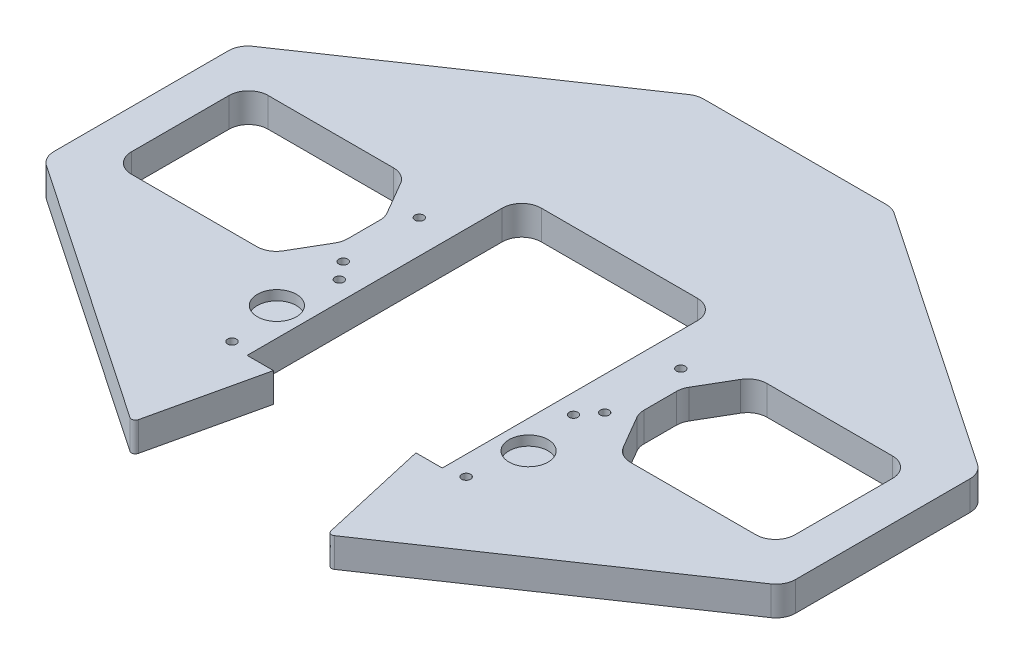
SolidWorks part; units mm, degrees
material "Balsa"
ref_plane "Plan de face" through (0, 0, 0) normal (0, 0, 1) x (1, 0, 0)
ref_plane "Plan de dessus" through (0, 0, 0) normal (0, 1, 0) x (1, 0, 0)
ref_plane "Plan de droite" through (0, 0, 0) normal (1, 0, 0) x (0, 0, -1)
sketch "Esquisse1" plane through (0, 0, 0) normal (0, 1, 0) x (1, 0, 0)
  line L0 (-76.6432, -51.4013) -> (63.3568, 43.5987)
  line L1 (63.3568, 43.5987) -> (163.3568, 43.5987)
  line L2 (-76.6432, -51.4013) -> (-76.6432, -151.4013)
  line L3 (63.3568, -246.4013) -> (163.3568, -246.4013)
  line L4 (303.3568, -51.4013) -> (303.3568, -151.4013)
  line L5 (163.3568, 43.5987) -> (303.3568, -51.4013)
  line L6 (163.3568, -246.4013) -> (303.3568, -151.4013)
  line L7 (-76.6432, -151.4013) -> (63.3568, -246.4013)
  point P0 (-76.6432, 43.5987)
  point P1 (303.3568, -246.4013)
  point P2 (-76.6432, -246.4013)
  point P3 (303.3568, 43.5987)
  dimension "D1" = 380
  dimension "D2" = 290
  dimension "D3" = 140
  dimension "D4" = 95
  dimension "D5" = 140
  dimension "D6" = 95
  dimension "D7" = 140
  dimension "D8" = 95
  dimension "D9" = 95
  dimension "D10" = 140
extrude "Boss.-Extru.1" add sketch "Esquisse1" along normal blind 15 contours L0 L1 L5 L4 L6 L3 L7 L2
sketch "Esquisse6" plane through (0, 0, 246.4013) normal (0, 0, 1) x (1, 0, 0)
  line L1 (63.3568, 15) -> (163.3568, 15)
  line L2 (63.3568, 15) -> (63.3568, 0)
  line L3 (63.3568, 0) -> (163.3568, 0)
  line L4 (163.3568, 15) -> (163.3568, 0)
extrude "Enlèv. mat.-Extru.1" cut sketch "Esquisse6" against normal blind 200
sketch "Esquisse7" plane through (0, 15, 0) normal (0, 1, 0) x (1, 0, 0)
  line L0 (-76.6432, -51.4013) -> (-76.6432, -151.4013) construction
  line L1 (23.3568, -136.4013) -> (-56.6432, -136.4013)
  line L2 (23.3568, -136.4013) -> (23.3568, -66.4013)
  line L3 (23.3568, -66.4013) -> (-56.6432, -66.4013)
  line L4 (-56.6432, -136.4013) -> (-56.6432, -66.4013)
  line L5 (163.3568, -46.4013) -> (63.3568, -46.4013) construction
  line L6 (303.3568, -51.4013) -> (303.3568, -151.4013) construction
  line L7 (283.3568, -136.4013) -> (203.3568, -136.4013)
  line L8 (283.3568, -136.4013) -> (283.3568, -66.4013)
  line L9 (283.3568, -66.4013) -> (203.3568, -66.4013)
  line L10 (203.3568, -136.4013) -> (203.3568, -66.4013)
  dimension "D1" = 70
  dimension "D2" = 20
  dimension "D3" = 80
  dimension "D4" = 20
  dimension "D5" = 70
  dimension "D6" = 80
  dimension "D7" = 20
  dimension "D8" = 20
extrude "Enlèv. mat.-Extru.2" cut sketch "Esquisse7" against normal up to next
sketch "Esquisse8" plane through (0, 15, 0) normal (0, 1, 0) x (1, 0, 0)
  line L0 (203.3568, -66.4013) -> (203.3568, -136.4013) construction
  line L1 (203.3568, -136.4013) -> (283.3568, -136.4013) construction
  line L2 (23.3568, -136.4013) -> (23.3568, -66.4013) construction
  line L3 (-56.6432, -136.4013) -> (23.3568, -136.4013) construction
  circle A0 centre (180.3568, -120.9013) radius 2.25
  circle A1 centre (180.3568, -81.9013) radius 2.25
  circle A2 centre (46.3568, -120.9013) radius 2.25
  circle A3 centre (46.3568, -81.9013) radius 2.25
  dimension "D1" = 4.5
  dimension "D3" = 4.5
  dimension "D11" = 4.5
  dimension "D12" = 4.5
  dimension "D2" = 23
  dimension "D4" = 23
  dimension "D5" = 39
  dimension "D6" = 15.5
  dimension "D7" = 23
  dimension "D8" = 23
  dimension "D9" = 39
  dimension "D10" = 15.5
extrude "Enlèv. mat.-Extru.4" cut sketch "Esquisse8" against normal up to next contours A0 | A2 | A1 | A3
sketch "Esquisse9" plane through (0, 15, 0) normal (0, 1, 0) x (1, 0, 0)
  line L0 (203.3568, -66.4013) -> (203.3568, -136.4013) construction
  line L1 (203.3568, -90.4013) -> (189.3568, -90.4013)
  line L2 (203.3568, -90.4013) -> (203.3568, -112.4013)
  line L3 (203.3568, -112.4013) -> (189.3568, -112.4013)
  line L4 (189.3568, -90.4013) -> (189.3568, -112.4013)
  line L5 (23.3568, -136.4013) -> (23.3568, -66.4013) construction
  line L6 (23.3568, -112.4013) -> (37.3568, -112.4013)
  line L7 (23.3568, -112.4013) -> (23.3568, -90.4013)
  line L8 (23.3568, -90.4013) -> (37.3568, -90.4013)
  line L9 (37.3568, -112.4013) -> (37.3568, -90.4013)
  dimension "D1" = 14
  dimension "D2" = 22
  dimension "D3" = 24
  dimension "D4" = 22
  dimension "D5" = 14
  dimension "D6" = 24
extrude "Enlèv. mat.-Extru.5" cut sketch "Esquisse9" against normal up to next
sketch "Esquisse10" plane through (0, 15, 0) normal (0, 1, 0) x (1, 0, 0)
  line L0 (25.0868, -68.1554) -> (23.3568, -66.4013)
  line L1 (23.3568, -66.4013) -> (-56.6432, -66.4013) construction
  line L2 (23.3568, -90.4013) -> (23.3568, -66.4013) construction
  line L3 (23.3568, -66.4013) -> (37.3568, -90.4013)
  line L4 (37.3568, -90.4013) -> (23.3568, -90.4013)
  line L5 (23.3568, -90.4013) -> (23.3568, -66.4013)
  line L6 (23.3568, -136.4013) -> (37.3568, -112.4013)
  line L7 (23.3568, -112.4013) -> (37.3568, -112.4013) construction
  line L8 (37.3568, -112.4013) -> (23.3568, -112.4013)
  line L9 (23.3568, -112.4013) -> (23.3568, -136.4013)
  line L10 (189.3568, -90.4013) -> (203.3568, -66.4013)
  line L12 (203.3568, -66.4013) -> (203.3568, -90.4013)
  line L13 (203.3568, -90.4013) -> (189.3568, -90.4013)
  line L14 (189.3568, -112.4013) -> (203.3568, -136.4013)
  line L15 (203.3568, -136.4013) -> (203.3568, -112.4013)
  line L16 (203.3568, -112.4013) -> (189.3568, -112.4013)
  line M1 (23.3568, -90.4013) -> (37.3568, -90.4013)
  line M3 (37.3568, -112.4013) -> (23.3568, -112.4013)
  line M4 (23.3568, -112.4013) -> (23.3568, -136.4013)
  line M8 (23.3568, -66.4013) -> (23.3568, -90.4013)
  line M9 (203.3568, -112.4013) -> (189.3568, -112.4013)
  line M11 (189.3568, -90.4013) -> (203.3568, -90.4013)
  line M12 (203.3568, -90.4013) -> (203.3568, -66.4013)
  line M16 (203.3568, -136.4013) -> (203.3568, -112.4013)
extrude "Enlèv. mat.-Extru.6" cut sketch "Esquisse10" against normal up to next contours L6 M4 M3 | L3 M8 M1 | M12 M11 | L14 M9 M16 region at (28.0235, 15, 82.4013) region at (28.0235, 15, 120.4013) region at (198.6901, 15, 82.4013) region at (198.6901, 15, 120.4013)
fillet "Congé2" radius 10 4 edges at (203.3568, 7.5, 136.4013) (203.3568, 7.5, 66.4013) (189.3568, 7.5, 112.4013) (189.3568, 7.5, 90.4013)
fillet "Congé3" radius 10 4 edges at (23.3568, 7.5, 136.4013) (37.3568, 7.5, 112.4013) (37.3568, 7.5, 90.4013) (23.3568, 7.5, 66.4013)
fillet "Congé4" radius 10 4 edges at (283.3568, 7.5, 136.4013) (283.3568, 7.5, 66.4013) (-56.6432, 7.5, 136.4013) (-56.6432, 7.5, 66.4013)
fillet "Congé5" radius 10 4 edges at (-76.6432, 7.5, 51.4013) (-76.6432, 7.5, 151.4013) (303.3568, 7.5, 51.4013) (303.3568, 7.5, 151.4013)
fillet "Congé6" radius 10 2 edges at (163.3568, 7.5, -43.5987) (63.3568, 7.5, -43.5987)
sketch "Esquisse11" plane through (0, 15, 0) normal (0, 1, 0) x (1, 0, 0)
  line L0 (63.3568, -46.4013) -> (63.3568, -246.4013) construction
  line L1 (163.3568, -46.4013) -> (163.3568, -246.4013) construction
  circle A0 centre (53.3568, -129.9013) radius 2.25
  circle A1 centre (53.3568, -184.9013) radius 2.25
  circle A2 centre (173.3568, -129.9013) radius 2.25
  circle A3 centre (173.3568, -184.9013) radius 2.25
  dimension "D1" = 4.5
  dimension "D2" = 4.5
  dimension "D6" = 4.5
  dimension "D7" = 4.5
  dimension "D3" = 55
  dimension "D4" = 10
  dimension "D5" = 55
  dimension "D8" = 10
  dimension "D9" = 10
  dimension "D10" = 10
  dimension "D11" = 61.5
  dimension "D12" = 61.5
extrude "Enlèv. mat.-Extru.7" cut sketch "Esquisse11" against normal up to next
fillet "Congé7" radius 10 2 edges at (163.3568, 7.5, 46.4013) (63.3568, 7.5, 46.4013)
sketch "Esquisse12" plane through (0, 15, 0) normal (0, 1, 0) x (1, 0, 0)
  line L0 (63.3568, -246.4013) -> (76.8568, -187.1513)
  line L1 (76.8568, -187.1513) -> (63.3568, -187.1513)
  line L2 (63.3568, -56.4013) -> (63.3568, -246.4013) construction
  line L3 (63.3568, -187.1513) -> (63.3568, -246.4013)
  line L4 (163.3568, -187.1513) -> (163.3568, -246.4013)
  line L5 (163.3568, -56.4013) -> (163.3568, -246.4013) construction
  line L6 (163.3568, -187.1513) -> (149.8568, -187.1513)
  line L7 (149.8568, -187.1513) -> (163.3568, -246.4013)
  line L8 (163.3568, -246.4013) -> (163.5147, -246.1805)
  dimension "D1" = 59.25
  dimension "D2" = 59.25
  dimension "D3" = 73
  dimension "D4" = 13.5
extrude "Boss.-Extru.3" add sketch "Esquisse12" against normal up to vertex (15 mm away) contours L4 L6 L7 | L0 L1 L3 up to point (163.3568, 0, 246.4013)
fillet "Congé9" radius 2 2 edges at (63.3568, 7.5, 246.4013) (163.3568, 7.5, 246.4013)
sketch "Esquisse13" plane through (0, 15, 0) normal (0, 1, 0) x (1, 0, 0)
  circle A0 centre (48.8568, -157.4013) radius 10
  circle A2 centre (53.3568, -129.9013) radius 2.25 construction
  circle A3 centre (53.3568, -184.9013) radius 2.25 construction
  circle A4 centre (177.8568, -157.4013) radius 10
  circle A5 centre (173.3568, -129.9013) radius 2.25 construction
  dimension "D1" = 20
  dimension "D4" = 20
  dimension "D2" = 27.5
  dimension "D3" = 4.5
  dimension "D5" = 27.5
  dimension "D6" = 4.5
extrude "Enlèv. mat.-Extru.8" cut sketch "Esquisse13" against normal blind 5 contours A4 | A0 region at (177.8568, 15, 157.4013)
